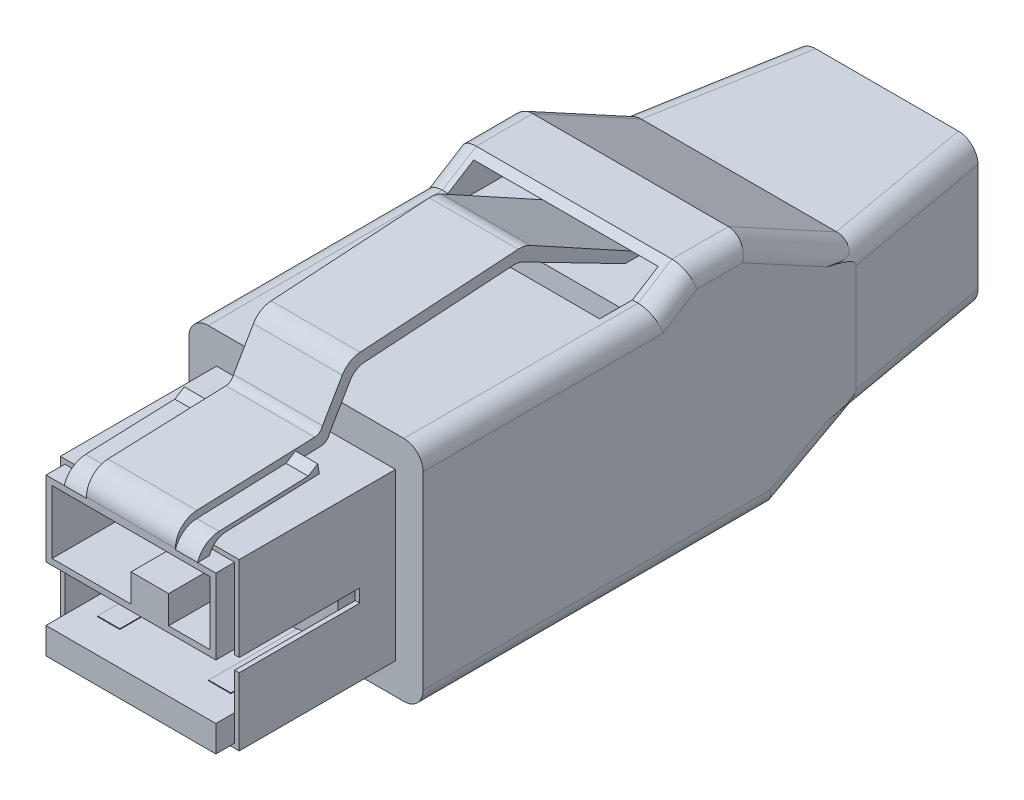
SolidWorks part; units mm, degrees
ref_plane "Plane1" through (0, 0, 0) normal (0, 0, 1) x (1, 0, 0)
ref_plane "Plane2" through (0, 0, 0) normal (0, 1, 0) x (1, 0, 0)
ref_plane "Plane3" through (0, 0, 0) normal (1, 0, 0) x (0, 0, -1)
sketch "Sketch1" plane through (0, 0, 0) normal (0, 0, 1) x (1, 0, 0)
  line L0 (0, 59.8) -> (0, -27.9) construction
  line L1 (-7.9, 7.685) -> (7.9, 7.685)
  line L2 (7.9, 7.685) -> (7.9, -7.685)
  line L3 (-7.9, 7.685) -> (-7.9, -7.685)
  line L4 (7.9, -7.685) -> (-7.9, -7.685)
  dimension "D1" = 15.8
  dimension "D2" = 15.37
  dimension "D3" = 7.685
extrude "Base-Extrude" add sketch "Sketch1" along normal blind 15.8
sketch "Sketch2" plane through (7.9, 0, 0) normal (1, 0, 0) x (0, 0, -1)
  line L0 (0, 7.685) -> (0, -7.685) construction
  line L1 (0, 7.685) -> (0, -7.685)
  line L2 (0, 7.685) -> (2.286, 9.115)
  line L3 (-15.8, -7.685) -> (0, -7.685) construction
  line L4 (2.286, 9.115) -> (6.096, 9.115)
  line L7 (13.41, 5.145) -> (13.41, -4.7196)
  line L8 (-15.8, 7.685) -> (-15.8, -7.685) construction
  line L9 (13.41, 5.145) -> (6.096, 9.115)
  line L10 (0, -7.685) -> (7.9461, -7.685)
  line L11 (7.9461, -7.685) -> (13.41, -4.7196)
  dimension "D1" = 16.8
  dimension "D2" = 2.286
  dimension "D3" = 3.81
  dimension "D5" = 29.21
extrude "Boss-Extrude1" add sketch "Sketch2" against normal up to surface (15.8 mm away) up to face at (-7.9, 0, 7.9)
sketch "Sketch3" plane through (0, 0, -13.41) normal (0, 0, -1) x (-1, 0, 0)
  line L4 (-7.9, -4.7196) -> (7.9, -4.7196)
  line L5 (7.9, -4.7196) -> (7.9, 5.145)
  line L6 (7.9, 5.145) -> (-7.9, 5.145)
  line L7 (-7.9, 5.145) -> (-7.9, -4.7196)
  line L8 (-7.9, -4.7196) -> (7.9, -4.7196)
  line L9 (7.9, -4.7196) -> (7.9, 5.145)
  line L10 (7.9, 5.145) -> (-7.9, 5.145)
  line L11 (-7.9, 5.145) -> (-7.9, -4.7196)
  dimension "D1" = 0
extrude "Boss-Extrude2" add sketch "Sketch3" along normal blind 9.99
sketch "Sketch5" plane through (0, 5.145, 0) normal (0, 1, 0) x (-1, 0, 0)
  line L0 (-7.9, -13.41) -> (-6.1385, -23.4)
  line L1 (7.9, -13.41) -> (6.1385, -23.4)
  line L2 (6.1385, -23.4) -> (7.9, -23.4)
  line L4 (-7.9, -23.4) -> (7.9, -23.4)
  line L5 (7.9, -23.4) -> (7.9, -13.41)
  line L6 (7.9, -13.41) -> (-7.9, -13.41)
  line L7 (-7.9, -13.41) -> (-7.9, -23.4)
  line L8 (-7.9, -23.4) -> (-6.1385, -23.4)
  line L9 (7.9, -23.4) -> (7.9, -13.41)
  line L11 (-7.9, -13.41) -> (-7.9, -23.4)
  dimension "D2" = 10
  dimension "D3" = 10
  dimension "D1" = 0
extrude "Cut-Extrude1" cut sketch "Sketch5" against normal through all
fillet "Fillet5" radius 1.3 12 edges at (-7.9, 7.13, -9.753) (-7.9, 9.115, -4.191) (-7.9, 8.4, -1.143) (-7.9, 7.685, 7.9) (7.9, 7.685, 7.9) (7.9, 8.4, -1.143) (7.9, 9.115, -4.191) (7.9, 7.13, -9.753) (7.9, -6.2023, -10.6781) (7.9, -7.685, 3.9269) (-7.9, -6.2023, -10.6781) (-7.9, -7.685, 3.9269)
fillet "Fillet6" radius 1.3 4 edges at (7.0192, 5.145, -18.405) (7.0192, -4.7196, -18.405) (-7.0192, -4.7196, -18.405) (-7.0192, 5.145, -18.405)
sketch "Sketch6" plane through (0, 0, -23.4) normal (0, 0, -1) x (-1, 0, 0)
  point P0 (0, 0)
sketch "Sketch7" plane through (0, 0, 15.8) normal (0, 0, 1) x (1, 0, 0)
  line L0 (-6.035, 5.59) -> (6.035, 5.59)
  line L1 (-6.035, 5.59) -> (-6.035, -5.59)
  line L2 (6.035, -5.59) -> (-6.035, -5.59)
  line L3 (6.035, -5.59) -> (6.035, 5.59)
  dimension "D1" = 11.18
  dimension "D2" = 12.07
  dimension "D3" = 6.035
  dimension "D4" = 5.59
extrude "Boss-Extrude3" add sketch "Sketch7" along normal blind 10.54
sketch "Sketch8" plane through (0, 0, 26.34) normal (0, 0, 1) x (1, 0, 0)
  line L12 (-5.73, 5.285) -> (-5.73, -5.285)
  line L13 (-5.73, -5.285) -> (5.73, -5.285)
  line L14 (5.73, -5.285) -> (5.73, 5.285)
  line L15 (5.73, 5.285) -> (-5.73, 5.285)
  line L16 (-5.73, 5.285) -> (-5.73, -5.285)
  line L17 (-5.73, -5.285) -> (5.73, -5.285)
  line L18 (5.73, -5.285) -> (5.73, 5.285)
  line L19 (5.73, 5.285) -> (-5.73, 5.285)
  dimension "D2" = 0.305
extrude "Cut-Extrude2" cut sketch "Sketch8" against normal up to surface (10.54 mm away) up to face at (0, 0, 15.8)
sketch "Sketch9" plane through (6.035, 0, 0) normal (1, 0, 0) x (0, 0, -1)
  line L0 (-26.34, -0.13) -> (-18.21, -0.13)
  line L2 (-18.21, -1.02) -> (-26.34, -1.02)
  line L3 (-18.21, -1.02) -> (-18.21, -0.13)
  line L4 (-26.34, -5.59) -> (-15.8, -5.59) construction
  line L5 (-26.34, -5.59) -> (-26.34, 5.59) construction
  line L10 (-15.8, 5.59) -> (-26.34, 5.59)
  line L11 (-26.34, 5.59) -> (-26.34, -5.59)
  line L12 (-26.34, -5.59) -> (-15.8, -5.59)
  line L13 (-15.8, -5.59) -> (-15.8, 5.59)
  line L15 (-26.34, -0.13) -> (-26.34, -1.02)
  dimension "D1" = 0.89
  dimension "D2" = 4.57
  dimension "D3" = 8.13
  dimension "D4" = 0
extrude "Cut-Extrude3" cut sketch "Sketch9" against normal through all
sketch "Sketch10" plane through (0, 0, 15.8) normal (0, 0, 1) x (1, 0, 0)
  line L1 (5.73, -3.505) -> (-5.73, -3.505)
  line L2 (5.73, 0.205) -> (5.73, 5.285)
  line L3 (-5.73, -3.505) -> (-5.73, -5.285)
  line L4 (5.73, 5.285) -> (-5.73, 5.285)
  line L5 (-5.73, 5.285) -> (-5.73, -5.285)
  line L6 (-5.73, -5.285) -> (5.73, -5.285)
  line L7 (5.73, -5.285) -> (5.73, 5.285)
  line L8 (5.73, 5.285) -> (-5.73, 5.285)
  line L9 (-5.73, 5.285) -> (-5.73, 0.205)
  line L10 (-5.73, -5.285) -> (5.73, -5.285)
  line L11 (5.73, -5.285) -> (5.73, -3.505)
  line L12 (5.73, 0.205) -> (-5.73, 0.205)
  dimension "D2" = 1.78
  dimension "D3" = 5.08
  dimension "D1" = 0
extrude "Boss-Extrude5" add sketch "Sketch10" along normal blind 11.81
sketch "Sketch11" plane through (0, 0, 15.8) normal (0, 0, 1) x (1, 0, 0)
  line L4 (-5.73, 0.205) -> (-5.73, -3.505)
  line L5 (-5.73, -3.505) -> (5.73, -3.505)
  line L6 (5.73, -3.505) -> (5.73, 0.205)
  line L7 (5.73, 0.205) -> (-5.73, 0.205)
  line L8 (-5.73, 0.205) -> (-5.73, -3.505)
  line L9 (-5.73, -3.505) -> (5.73, -3.505)
  line L10 (5.73, -3.505) -> (5.73, 0.205)
  line L11 (5.73, 0.205) -> (-5.73, 0.205)
  dimension "D1" = 0
extrude "Boss-Extrude6" add sketch "Sketch11" along normal blind 3.56
ref_plane "Plane4" through (6.223, 0, 0) normal (1, 0, 0) x (0, 0, -1)
sketch "Sketch12" plane through (6.223, 0, 0) normal (1, 0, 0) x (0, 0, -1)
  line L0 (1.7396, 8.7732) -> (5.1833, 8.7732)
  line L1 (2.286, 9.115) -> (0, 7.685) construction
  line L2 (5.1833, 8.7732) -> (5.1833, 6.8261)
  line L3 (5.1833, 6.8261) -> (0, 6.8261)
  line L4 (0, 6.8261) -> (-2.2082, 7.685)
  line L5 (0, 7.685) -> (-15.8, 7.685) construction
  line L6 (-2.2082, 7.685) -> (0, 7.685)
  line L7 (0, 7.685) -> (1.7396, 8.7732)
extrude "Cut-Extrude4" cut sketch "Sketch12" against normal blind 12.446
sketch "Sketch13" plane through (0, 0, 0) normal (1, 0, 0) x (0, 0, -1)
  line L1 (-14.8641, 9.8626) -> (-4.791, 10.5064)
  line L2 (-27.61, 5.3647) -> (-27.61, 5.285)
  line L3 (-4.1656, 10.376) -> (2.7362, 6.8261)
  line L4 (-26.1665, 6.8637) -> (-18.21, 7.1638)
  line L6 (-17.6827, 7.572) -> (-16.3512, 9.8547)
  line L7 (-15.1512, 10.5958) -> (-4.4811, 11.2777)
  line L8 (-3.6637, 11.0957) -> (4.1153, 6.8261)
  line L9 (5.1833, 6.8261) -> (0, 6.8261) construction
  line L10 (4.1153, 6.8261) -> (2.7362, 6.8261)
  line L13 (-25.7052, 6.1305) -> (-17.7612, 6.4302)
  line L14 (-17.2264, 6.8658) -> (-15.8241, 9.2697)
  line L25 (-27.61, 5.285) -> (-26.8067, 5.285)
  arc A0 (-15.8241, 9.2697) -> (-14.8641, 9.8626) centre (-14.7876, 8.6651) cw
  arc A1 (-26.8067, 5.285) -> (-25.7052, 6.1305) centre (-25.66, 4.9314) cw
  arc A2 (-26.1665, 6.8637) -> (-27.61, 5.3647) centre (-26.11, 5.3647) ccw
  arc A3 (-18.21, 7.1638) -> (-17.6827, 7.572) centre (-18.2316, 7.7364) ccw
  arc A4 (-16.3512, 9.8547) -> (-15.1512, 10.5958) centre (-15.0555, 9.0989) cw
  arc A5 (-4.791, 10.5064) -> (-4.1656, 10.376) centre (-4.7145, 9.3088) cw
  arc A7 (-17.7612, 6.4302) -> (-17.2264, 6.8658) centre (-17.7828, 7.0028) ccw
  arc A8 (-4.4811, 11.2777) -> (-3.6637, 11.0957) centre (-4.3854, 9.7808) cw
  dimension "D1" = 1.5
  dimension "D2" = 1.2
  dimension "D3" = 0.75
  dimension "D4" = 1.2
extrude "Boss-Extrude7" add sketch "Sketch13" along normal mid plane 6
sketch "Sketch15" plane through (3, 0, 0) normal (1, 0, 0) x (0, 0, -1)
  line L0 (-27.61, 5.285) -> (-26.8067, 5.285)
  line L1 (-19.4005, 6.3684) -> (-25.7052, 6.1305)
  line L2 (-19.4005, 6.3684) -> (-19.5087, 7.0028)
  line L3 (-19.5087, 7.0028) -> (-20.1497, 6.6037)
  line L4 (-20.1497, 6.6037) -> (-26.1665, 6.385)
  arc A0 (-25.7052, 6.1305) -> (-26.8067, 5.285) centre (-25.66, 4.9314) ccw
  arc A1 (-26.1665, 6.385) -> (-27.61, 5.285) centre (-26.1094, 4.813) ccw
extrude "Boss-Extrude8" add sketch "Sketch15" along normal blind 1.5
mirror "Mirror1" about plane through (0, 0, 0) normal (1, 0, 0) of "Boss-Extrude8"
sketch "Sketch16" plane through (0, 0, 27.61) normal (0, 0, 1) x (1, 0, 0)
  line L10 (0.006, 2.495) -> (0.006, 0.611)
  line L11 (2.546, 2.495) -> (2.546, 0.611)
  line L12 (2.546, 2.495) -> (0.006, 2.495)
  line L13 (2.546, 0.611) -> (5.324, 0.611)
  line L40 (5.324, 4.879) -> (4.5, 4.879)
  line L41 (4.5, 4.879) -> (2.594, 4.879)
  line L42 (2.594, 4.879) -> (2.594, 4.9587)
  line L43 (2.594, 4.9587) -> (-2.594, 4.9587)
  line L44 (-2.594, 4.9587) -> (-2.594, 4.879)
  line L45 (-2.594, 4.879) -> (-4.5, 4.879)
  line L46 (-4.5, 4.879) -> (-5.324, 4.879)
  line L47 (-5.324, 4.879) -> (-5.324, 0.611)
  line L48 (-5.324, 0.611) -> (5.324, 0.611)
  line L49 (5.324, 0.611) -> (5.324, 4.879)
  line L55 (5.324, 4.879) -> (-4.5, 4.879)
  line L56 (-4.5, 4.879) -> (-5.324, 4.879)
  line L57 (-5.324, 4.879) -> (-5.324, 0.611)
  line L58 (-5.324, 0.611) -> (0.006, 0.611)
  line L59 (5.324, 0.611) -> (5.324, 4.879)
  dimension "D1" = 5.33
  dimension "D3" = 2.54
  dimension "D4" = 1.884
  dimension "D2" = 0.406
extrude "Cut-Extrude5" cut sketch "Sketch16" against normal up to surface (8.25 mm away) up to face at (0, -1.1125, 19.36)
sketch "Sketch17" plane through (0, 0, 19.36) normal (0, 0, 1) x (1, 0, 0)
  line L0 (-4.5, 4.1257) -> (-3, 4.1257)
  line L1 (-4.5, 4.1257) -> (-4.5, 3.845)
  line L2 (-3, 3.845) -> (-4.5, 3.845)
  line L3 (-3, 3.845) -> (-3, 4.1257)
  line L4 (-2, 4.1124) -> (-0.5, 4.1124)
  line L5 (-2, 4.1124) -> (-2, 3.8317)
  line L6 (-0.5, 3.8317) -> (-2, 3.8317)
  line L7 (-0.5, 3.8317) -> (-0.5, 4.1124)
  line L8 (0.5, 4.0879) -> (2, 4.0879)
  line L9 (0.5, 4.0879) -> (0.5, 3.8072)
  line L10 (2, 3.8072) -> (0.5, 3.8072)
  line L11 (2, 3.8072) -> (2, 4.0879)
  line L12 (3, 4.0389) -> (4.5, 4.0389)
  line L13 (3, 4.0389) -> (3, 3.7582)
  line L14 (4.5, 3.7582) -> (3, 3.7582)
  line L15 (4.5, 3.7582) -> (4.5, 4.0389)
  line L16 (-5.324, 4.879) -> (-5.324, 0.611) construction
  line L17 (5.324, 0.611) -> (5.324, 4.879) construction
  dimension "D1" = 1.5
  dimension "D2" = 1
  dimension "D3" = 1.5
  dimension "D4" = 1
  dimension "D5" = 1.5
  dimension "D6" = 1
  dimension "D7" = 0.824
  dimension "D8" = 0.824
extrude "Boss-Extrude9" add sketch "Sketch17" along normal blind 6
sketch "Sketch18" plane through (0, 0, 25.36) normal (0, 0, 1) x (1, 0, 0)
  line L4 (-2, 4.1124) -> (-2, 3.8317)
  line L5 (-2, 3.8317) -> (-0.5, 3.8317)
  line L6 (-0.5, 3.8317) -> (-0.5, 4.1124)
  line L7 (-0.5, 4.1124) -> (-2, 4.1124)
  line L8 (-2, 4.1124) -> (-2, 3.8317)
  line L9 (-2, 3.8317) -> (-0.5, 3.8317)
  line L10 (-0.5, 3.8317) -> (-0.5, 4.1124)
  line L11 (-0.5, 4.1124) -> (-2, 4.1124)
  line L13 (0.5, 4.0879) -> (0.5, 3.8072)
  line L14 (0.5, 3.8072) -> (2, 3.8072)
  line L15 (2, 3.8072) -> (2, 4.0879)
  line L16 (2, 4.0879) -> (0.5, 4.0879)
  line L17 (0.5, 4.0879) -> (0.5, 3.8072)
  line L18 (0.5, 3.8072) -> (2, 3.8072)
  line L19 (2, 3.8072) -> (2, 4.0879)
  line L20 (2, 4.0879) -> (0.5, 4.0879)
  dimension "D1" = 0
  dimension "D2" = 0
extrude "Cut-Extrude6" cut sketch "Sketch18" against normal blind 1.5
sketch "Sketch19" plane through (0, -3.505, 0) normal (0, 1, 0) x (-1, 0, 0)
  line L0 (-4.5, 19.36) -> (-3, 19.36)
  line L1 (-4.5, 19.36) -> (-4.5, 25.36)
  line L2 (-3, 25.36) -> (-4.5, 25.36)
  line L3 (-3, 25.36) -> (-3, 19.36)
  line L4 (-2, 19.36) -> (-0.5, 19.36)
  line L5 (-2, 19.36) -> (-2, 23.86)
  line L6 (-0.5, 23.86) -> (-2, 23.86)
  line L7 (-0.5, 23.86) -> (-0.5, 19.36)
  line L8 (0.5, 19.36) -> (2, 19.36)
  line L9 (0.5, 19.36) -> (0.5, 23.86)
  line L10 (2, 23.86) -> (0.5, 23.86)
  line L11 (2, 23.86) -> (2, 19.36)
  line L12 (3, 19.36) -> (4.5, 19.36)
  line L13 (3, 19.36) -> (3, 25.36)
  line L14 (4.5, 25.36) -> (3, 25.36)
  line L15 (4.5, 25.36) -> (4.5, 19.36)
extrude "Boss-Extrude10" add sketch "Sketch19" along normal blind 0.05
other "CPoint1"
ref_axis "Axis1" through (0, 0, -33.4) along (0, 0, 1)
